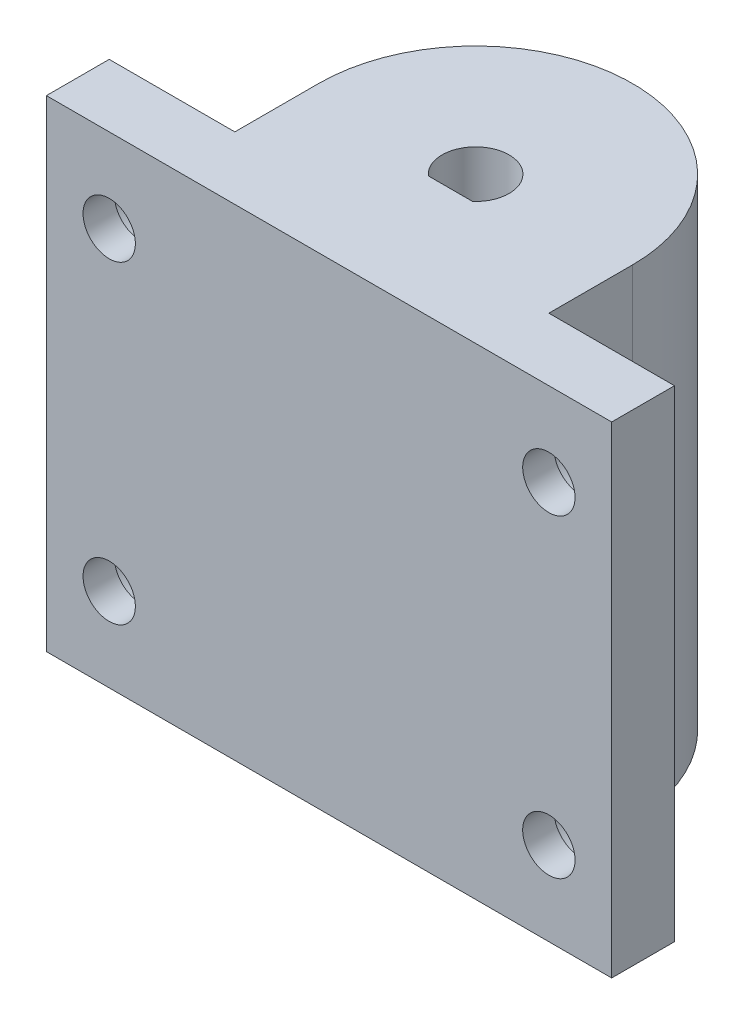
SolidWorks part; units mm, degrees
ref_plane "前视基准面" through (0, 0, 0) normal (0, 0, 1) x (1, 0, 0)
ref_plane "上视基准面" through (0, 0, 0) normal (0, 1, 0) x (1, 0, 0)
ref_plane "右视基准面" through (0, 0, 0) normal (1, 0, 0) x (0, 0, -1)
other "Configuration Table"
sketch "草图2" plane through (0, 0, 0) normal (0, 1, 0) x (1, 0, 0)
  line L9 (0, 0) -> (170, 0)
  line L10 (0, 0) -> (0, -20)
  line L11 (0, -20) -> (170, -20)
  line L12 (170, 0) -> (170, -20)
  dimension "D1" = 170
  dimension "D2" = 20
extrude "凸台-拉伸1" add sketch "草图2" along normal blind 23
sketch "草图3" plane through (0, 23, 0) normal (0, 1, 0) x (1, 0, 0)
  line L0 (123.9417, -11.2) -> (126.0583, -11.2)
  line L1 (158.9417, -11.2) -> (161.0583, -11.2)
  line L2 (0, -20) -> (170, -20) construction
  line L3 (170, -20) -> (170, 0) construction
  circle A0 centre (125, -10) radius 1.6
  circle A1 centre (160, -10) radius 1.6
  dimension "D1" = 3.2
  dimension "D2" = 10
  dimension "D3" = 45
  dimension "D4" = 10
  dimension "D5" = 10
  dimension "D6" = 1.2
extrude "切除-拉伸1" cut sketch "草图3" against normal through all contours L1 A1 | L0 A0 region at (125, 23, 9.8941) region at (160, 23, 9.8941)
sketch "草图4" plane through (170, 0, 0) normal (1, 0, 0) x (0, 0, -1)
  line L0 (0, 23) -> (0, 0) construction
  line L1 (0, 18) -> (-17, 18)
  line L2 (0, 18) -> (0, 5)
  line L3 (0, 5) -> (-17, 5)
  line L4 (-17, 18) -> (-17, 5)
  line L5 (-17, 18) -> (-17, 23)
  line L6 (-20, 23) -> (0, 23) construction
  line L7 (-17, 5) -> (-17, 0)
  line L8 (-20, 0) -> (0, 0) construction
  line L9 (-20, 23) -> (-20, 0) construction
  line M6 (0, 0) -> (0, 23)
  dimension "D1" = 13
  dimension "D2" = 3
extrude "切除-拉伸2" cut sketch "草图4" against normal blind 30 contours L1 L4 L3 M6 region at (170, 11.5, 8.5)
sketch "草图5" plane through (0, 23, 0) normal (0, 1, 0) x (1, 0, 0)
  line L0 (117.5, -10) -> (117.5, -20)
  line L1 (0, -20) -> (170, -20) construction
  line L2 (132.5, -10) -> (132.5, -20)
  line L3 (152.5, -10) -> (152.5, -20)
  line L4 (167.5, -10) -> (167.5, -20)
  line L5 (132.5, -17) -> (152.5, -17)
  line L6 (167.5, -17) -> (170, -17)
  line L7 (170, -20) -> (170, 0) construction
  line L8 (132.5, -17) -> (102.5, -17)
  line L9 (102.5, -17) -> (102.5, 0)
  line L10 (170, 0) -> (0, 0) construction
  line L11 (102.5, -17) -> (102.5, -20)
  circle A0 centre (125, -10) radius 7.5
  circle A1 centre (160, -10) radius 7.5
  arc A2 (126.0583, -11.2) -> (123.9417, -11.2) centre (125, -10) ccw construction
  arc A3 (161.0583, -11.2) -> (158.9417, -11.2) centre (160, -10) ccw construction
  line M10 (0, 0) -> (0, -20)
  line M11 (0, -20) -> (170, -20)
  line M12 (170, -20) -> (170, 0)
  line M13 (170, 0) -> (0, 0)
  dimension "D1" = 15
  dimension "D2" = 3
  dimension "D3" = 30
extrude "切除-拉伸3" cut sketch "草图5" against normal through all contours L8 L9 L0 M13 M10 M11 | A1 L4 L6 L9 L8 L0 A0 L2 L5 L3 M12 M13 region at (133.0731, 23, 7.5108) region at (51.25, 23, 10)
sketch "草图6" plane through (0, 23, 0) normal (0, 1, 0) x (1, 0, 0)
  line L1 (102.5, -17) -> (170, -17)
  line L2 (102.5, -17) -> (102.5, -20)
  line L3 (102.5, -20) -> (170, -20)
  line L4 (170, -17) -> (170, -20)
  line L5 (152.5, -17) -> (170, -17)
  line L6 (152.5, -17) -> (152.5, -2.5)
  line L7 (152.5, -2.5) -> (170, -2.5)
  line L8 (170, -17) -> (170, -2.5)
  arc A0 (167.5, -10) -> (152.5, -10) centre (160, -10) ccw construction
extrude "切除-拉伸4" cut sketch "草图6" against normal through all contours L4 L3 L2 L1 | L5 L6 L7 L8
sketch "草图7" plane through (0, 0, 17) normal (0, 0, 1) x (1, 0, 0)
  line L0 (117.5, 0) -> (132.5, 0) construction
  line L1 (111.5, 23) -> (138.5, 23)
  line L2 (111.5, 23) -> (111.5, 0)
  line L3 (111.5, 0) -> (138.5, 0)
  line L4 (138.5, 23) -> (138.5, 0)
  line L5 (117.5, 23) -> (132.5, 23) construction
  line L6 (117.5, 0) -> (117.5, 23) construction
  line L7 (132.5, 0) -> (132.5, 23) construction
  circle A0 centre (114.5, 19) radius 2
  circle A1 centre (114.5, 19) radius 1.25
  circle A2 centre (114.5, 4) radius 2
  circle A3 centre (114.5, 4) radius 1.25
  circle A4 centre (135.5, 4) radius 1.25
  circle A5 centre (135.5, 4) radius 2
  circle A6 centre (135.5, 19) radius 1.25
  circle A7 centre (135.5, 19) radius 2
  point P24 (0, 0)
  point P25 (0, 0)
  point P26 (0, 0)
  point P27 (0, 0)
  point P28 (0, 0)
  dimension "D3" = 2.5
  dimension "D4" = 4
  dimension "D1" = 6
  dimension "D2" = 6
  dimension "D5" = 4
  dimension "D6" = 3
  dimension "D7" = 4
  dimension "D8" = 3
extrude "凸台-拉伸2" add sketch "草图7" against normal blind 3 contours L2 L3 L4 L1 | A1 | A3 | A4 | A6
extrude "切除-拉伸5" cut sketch "草图7<3>" along normal blind 1.5 from surface contours A2 | A0 | A7 | A5 starting at face at (115.75, 4, 14)
sketch "草图7<3>" plane through (0, 0, 17) normal (0, 0, 1) x (1, 0, 0) same geometry as "草图7"
